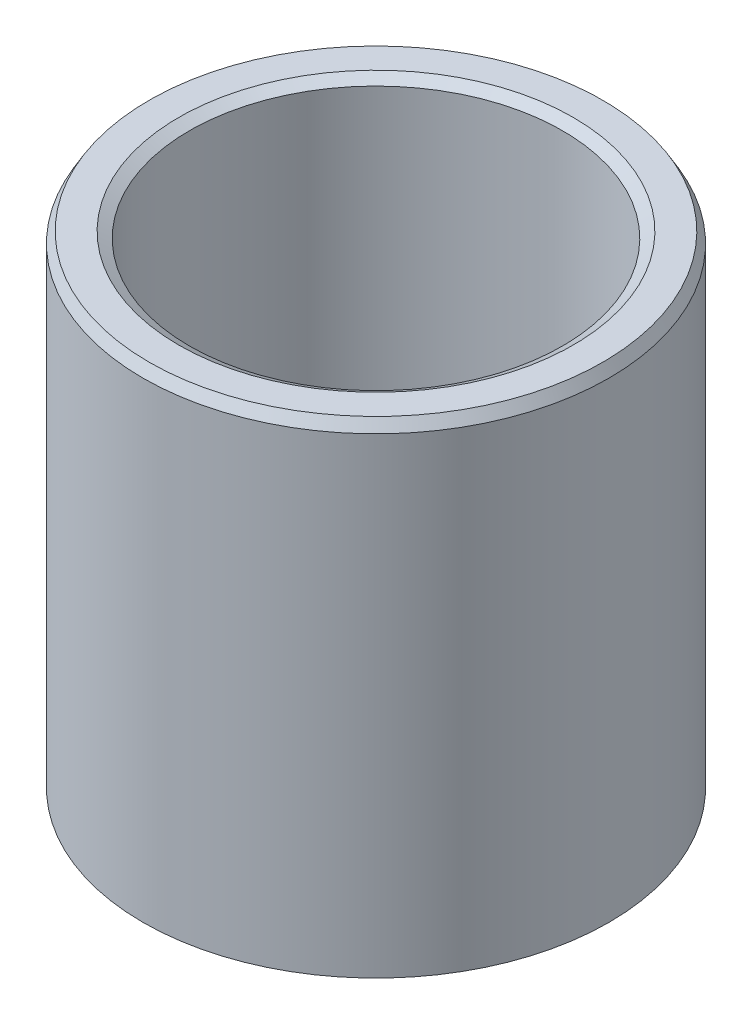
SolidWorks part; units mm, degrees
ref_plane "Front Plane" through (0, 0, 0) normal (0, 0, 1) x (1, 0, 0)
ref_plane "Top Plane" through (0, 0, 0) normal (0, 1, 0) x (1, 0, 0)
ref_plane "Right Plane" through (0, 0, 0) normal (1, 0, 0) x (0, 0, -1)
sketch "Sketch1" plane through (0, 0, 0) normal (0, 1, 0) x (1, 0, 0)
  circle A0 centre (0, 0) radius 60
  dimension "SLEEVE_OD" = 120
extrude "Boss-Extrude1" add sketch "Sketch1" along normal blind 125.7006
sketch "Sketch2" plane through (0, 0, 0) normal (0, 1, 0) x (1, 0, 0)
  circle A0 centre (0, 0) radius 48.0281
  dimension "BORE_D" = 96.0561
extrude "Cut-Extrude1" cut sketch "Sketch2" along normal through all
chamfer "Chamfer1" distance 2.7515 angle 30 4 edges at (0, 125.7006, 48.0281) (0, 0, 48.0281) (0, 0, 60) (0, 125.7006, 60) first distance on face at (0, 125.7006, 48.0281) first distance on face at (0, 0, 48.0281) first distance on face at (0, 125.7006, 60)
